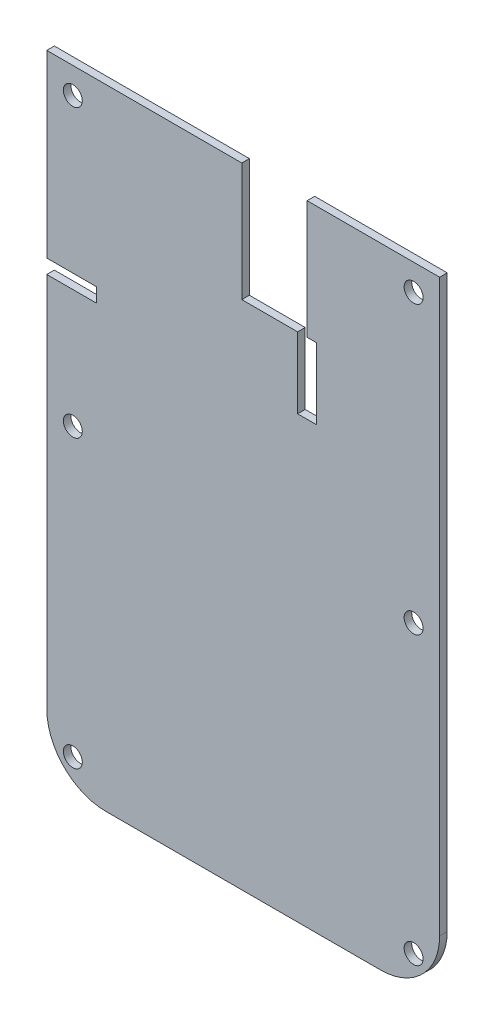
SolidWorks part; units mm, degrees
ref_plane "前视基准面" through (0, 0, 0) normal (0, 0, 1) x (1, 0, 0)
ref_plane "上视基准面" through (0, 0, 0) normal (0, 1, 0) x (1, 0, 0)
ref_plane "右视基准面" through (0, 0, 0) normal (1, 0, 0) x (0, 0, -1)
sketch "草图1" plane through (0, 0, 0) normal (0, 0, 1) x (1, 0, 0)
  line L1 (-41.5, 66.5) -> (0, 66.5)
  line L2 (-41.5, 66.5) -> (-41.5, 6.25)
  line L3 (-35.25, 0) -> (-6.25, 0)
  line L4 (0, 66.5) -> (0, 6.25)
  arc A0 (-6.25, 0) -> (0, 6.25) centre (-6.25, 6.25) ccw
  arc A1 (-35.25, 0) -> (-41.5, 6.25) centre (-35.25, 6.25) cw
  point P6 (0, 0)
  point P7 (0, 66.5)
  point P10 (-41.5, 66.5)
  point P13 (-41.5, 0)
  dimension "D3" = 6.25
  dimension "D1" = 41.5
  dimension "D2" = 66.5
extrude "凸台-拉伸1" add sketch "草图1" along normal blind 0.8 contours L2 A1 L3 A0 L4 L1
sketch "草图2" plane through (0, 0, 0.8) normal (0, 0, 1) x (1, 0, 0)
  line L0 (-41.5, 66.5) -> (-41.5, 6.25) construction
  line L1 (-41.5, 66.5) -> (0, 66.5) construction
  line L2 (-38.75, 63.75) -> (-38.75, 33.5) construction
  line L3 (-20.75, -943.2655) -> (-20.75, 49056.7345) construction
  line L4 (0, 66.5) -> (0, 6.25) construction
  line L11 (-41.5, 66.5) -> (-41.5, 6.25) construction
  line L12 (-41.5, 47.5) -> (-36.25, 47.5)
  line L13 (-41.5, 47.5) -> (-41.5, 46)
  line L14 (-41.5, 46) -> (-36.25, 46)
  line L15 (-36.25, 47.5) -> (-36.25, 46)
  line L16 (-41.5, 66.5) -> (0, 66.5) construction
  line L17 (0, 66.5) -> (0, 6.25) construction
  line L18 (-13, 54) -> (-15, 54)
  line L19 (-13, 54) -> (-13, 46.5)
  line L20 (-13, 46.5) -> (-15, 46.5)
  line L21 (-15, 54) -> (-15, 46.5)
  circle A0 centre (-38.75, 63.75) radius 1
  circle A1 centre (-38.75, 33.5) radius 1
  circle A2 centre (-38.75, 3.25) radius 1
  circle A3 centre (-2.75, 3.25) radius 1
  circle A4 centre (-2.75, 33.5) radius 1
  circle A5 centre (-2.75, 63.75) radius 1
  dimension "D1" = 2
  dimension "D2" = 2.75
  dimension "D3" = 2.75
  dimension "D5" = 30.25
  dimension "D6" = 5.25
  dimension "D7" = 1.5
  dimension "D8" = 19
  dimension "D9" = 2
  dimension "D10" = 7.5
  dimension "D11" = 12.5
  dimension "D12" = 13
  dimension "D4" = 3
extrude "切除-拉伸1" cut sketch "草图2" against normal through all
sketch "草图3" plane through (0, 0, 0.8) normal (0, 0, 1) x (1, 0, 0)
  line L0 (-41.5, 66.5) -> (0, 66.5) construction
  line L1 (-14, 54) -> (-20.9, 54)
  line L2 (-14, 54) -> (-14, 66.5)
  line L3 (-14, 66.5) -> (-20.9, 66.5)
  line L4 (-20.9, 54) -> (-20.9, 66.5)
  line L5 (0, 66.5) -> (0, 6.25) construction
  dimension "D1" = 12.5
  dimension "D2" = 14
  dimension "D3" = 6.9
extrude "切除-拉伸2" cut sketch "草图3" against normal through all
